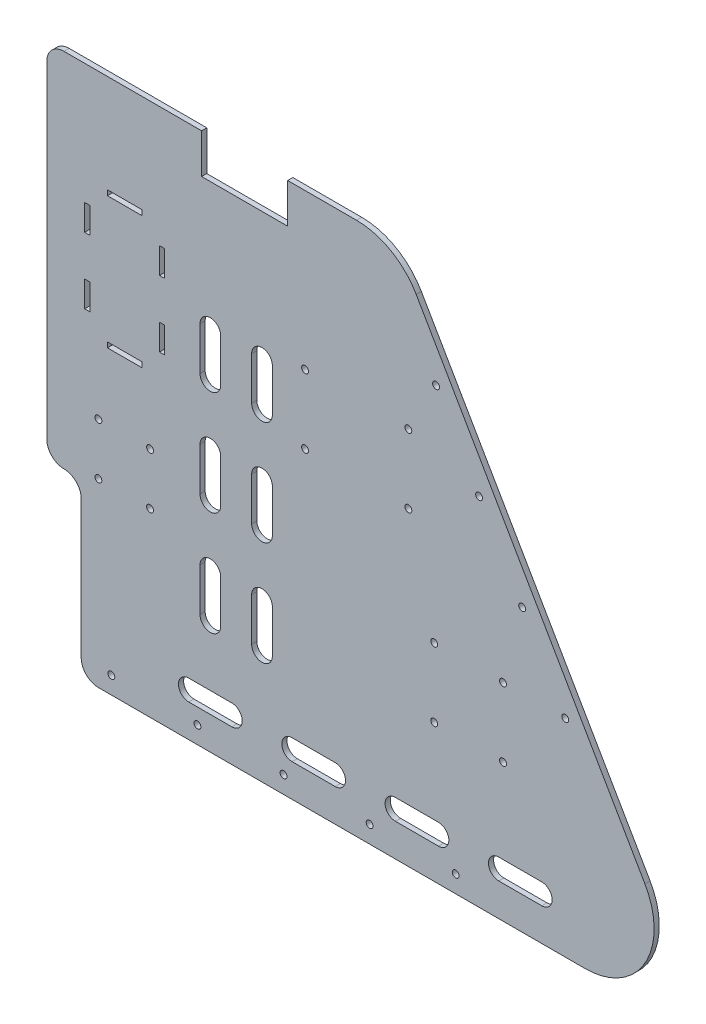
SolidWorks part; units mm, degrees
material "红木"
ref_plane "前视基准面" through (0, 0, 0) normal (0, 0, 1) x (1, 0, 0)
ref_plane "上视基准面" through (0, 0, 0) normal (0, 1, 0) x (1, 0, 0)
ref_plane "右视基准面" through (0, 0, 0) normal (1, 0, 0) x (0, 0, -1)
sketch "草图1" plane through (0, 0, 0) normal (0, 0, 1) x (1, 0, 0)
  line L0 (0, 0) -> (337.718, 0)
  line L1 (0, 0) -> (0, 310)
  line L2 (0, 310) -> (204.9274, 310)
  line L3 (239.5684, 290) -> (372.359, 60)
  line L4 (0, 66) -> (25, 66)
  line L5 (25, 66) -> (25, 310)
  line L7 (164.9274, 310) -> (114.9274, 310)
  line L8 (164.9274, 310) -> (164.9274, 287)
  line L9 (164.9274, 287) -> (114.9274, 287)
  line L10 (114.9274, 310) -> (114.9274, 287)
  arc A0 (337.718, 0) -> (372.359, 60) centre (337.718, 40) ccw
  arc A1 (239.5684, 290) -> (204.9274, 310) centre (204.9274, 270) ccw
  point P7 (407, 0)
  dimension "D4" = 40
  dimension "D1" = 407
  dimension "D2" = 310
  dimension "D3" = 60
  dimension "D5" = 25
  dimension "D6" = 66
  dimension "D7" = 23
  dimension "D8" = 50
  dimension "D9" = 40
extrude "凸台-拉伸1" add sketch "草图1" along normal blind 3 contours L3 A1 L2 L5 L4 L1 L0 A0 region at (170.7305, 136.5672, 0)
sketch "草图2" plane through (0, 0, 3) normal (0, 0, 1) x (1, 0, 0)
  line L0 (-53.0397, 10) -> (306.7383, 10) construction
  line L2 (0, 0) -> (337.718, 0) construction
  line L3 (0, 0) -> (0, 66) construction
  line L4 (337.718, 40) -> (19.1375, 223.9325) construction
  line L6 (262.5, 10) -> (212.5, 10) construction
  circle A0 centre (262.5, 10) radius 2
  circle A2 centre (212.5, 10) radius 2
  circle A3 centre (162.5, 10) radius 2
  circle A4 centre (112.5, 10) radius 2
  circle A5 centre (62.5, 10) radius 2
  circle A7 centre (251.0897, 250.0445) radius 2
  circle A8 centre (276.0897, 206.7432) radius 2
  circle A9 centre (301.0897, 163.4419) radius 2
  circle A10 centre (326.0897, 120.1407) radius 2
  dimension "D2" = 4
  dimension "D3" = 262.5
  dimension "D5" = 5
  dimension "D1" = 10
  dimension "D4" = 30
  dimension "D6" = 50
extrude "切除-拉伸1" cut sketch "草图2" against normal blind 10
sketch "草图3" plane through (0, 0, 3) normal (0, 0, 1) x (1, 0, 0)
  line L6 (0, 0) -> (45, 0)
  line L7 (0, 0) -> (0, 100)
  line L8 (0, 100) -> (45, 100)
  line L9 (45, 0) -> (45, 100)
  dimension "D1" = 100
  dimension "D2" = 45
extrude "切除-拉伸2" cut sketch "草图3" against normal through all
fillet "圆角1" radius 10 4 edges at (25, 310, 1.5) (25, 100, 1.5) (45, 100, 1.5) (45, 0, 1.5)
sketch "草图5" plane through (0, 0, 0) normal (0, 0, -1) x (-1, 0, 0)
  line L0 (-25, 110) -> (-25, 300) construction
  line L1 (-90.5, 250) -> (-50, 250) construction
  line L2 (-90.5, 250) -> (-90.5, 176.5) construction
  line L3 (-90.5, 176.5) -> (-50, 176.5) construction
  line L4 (-50, 250) -> (-50, 176.5) construction
  line L5 (-35, 310) -> (-114.9274, 310) construction
  line L6 (-70.25, 266.1718) -> (-70.25, 143.6965) construction
  line L7 (-90.5, 240) -> (-93.5, 240)
  line L8 (-90.5, 240) -> (-90.5, 225)
  line L9 (-90.5, 225) -> (-93.5, 225)
  line L10 (-93.5, 240) -> (-93.5, 225)
  line L11 (-90.5, 186.5) -> (-93.5, 186.5)
  line L12 (-90.5, 186.5) -> (-90.5, 201.5)
  line L13 (-90.5, 201.5) -> (-93.5, 201.5)
  line L14 (-93.5, 186.5) -> (-93.5, 201.5)
  line L15 (-50, 201.5) -> (-47, 201.5)
  line L16 (-47, 186.5) -> (-47, 201.5)
  line L17 (-50, 186.5) -> (-47, 186.5)
  line L18 (-50, 186.5) -> (-50, 201.5)
  line L19 (-50, 225) -> (-47, 225)
  line L20 (-47, 240) -> (-47, 225)
  line L21 (-50, 240) -> (-47, 240)
  line L22 (-50, 240) -> (-50, 225)
  line L24 (-60.25, 253) -> (-80.25, 253)
  line L25 (-60.25, 253) -> (-60.25, 250)
  line L26 (-60.25, 250) -> (-80.25, 250)
  line L27 (-80.25, 253) -> (-80.25, 250)
  line L28 (-60.25, 253) -> (-80.25, 250) construction
  line L29 (-60.25, 250) -> (-80.25, 253) construction
  line L30 (-80.25, 173.5) -> (-60.25, 173.5)
  line L31 (-80.25, 173.5) -> (-80.25, 176.5)
  line L32 (-80.25, 176.5) -> (-60.25, 176.5)
  line L33 (-60.25, 173.5) -> (-60.25, 176.5)
  line L34 (-80.25, 173.5) -> (-60.25, 176.5) construction
  line L35 (-80.25, 176.5) -> (-60.25, 173.5) construction
  point P14 (-92, 240)
  point P27 (-70.25, 251.5)
  point P32 (-70.25, 175)
  dimension "D1" = 73.5
  dimension "D2" = 40.5
  dimension "D3" = 25
  dimension "D4" = 60
  dimension "D5" = 15
  dimension "D6" = 3
  dimension "D7" = 10
  dimension "D8" = 15
  dimension "D9" = 3
  dimension "D10" = 10
  dimension "D11" = 20.25
  dimension "D12" = 3
  dimension "D13" = 20
  dimension "D14" = 3
  dimension "D15" = 20
extrude "大疆的电池" cut sketch "草图5" against normal blind 10
sketch "草图6" plane through (0, 0, 0) normal (0, 0, -1) x (-1, 0, 0)
  line L0 (-312.5, 25) -> (-287.5, 25) construction
  line L1 (-312.5, 31) -> (-287.5, 31)
  line L2 (-312.5, 19) -> (-287.5, 19)
  line L3 (-55, 0) -> (-337.718, 0) construction
  line L4 (-252.5, 19) -> (-227.5, 19)
  line L5 (-252.5, 31) -> (-227.5, 31)
  line L6 (-252.5, 25) -> (-227.5, 25) construction
  line L7 (-192.5, 19) -> (-167.5, 19)
  line L8 (-192.5, 31) -> (-167.5, 31)
  line L9 (-192.5, 25) -> (-167.5, 25) construction
  line L10 (-132.5, 19) -> (-107.5, 19)
  line L11 (-132.5, 31) -> (-107.5, 31)
  line L12 (-132.5, 25) -> (-107.5, 25) construction
  line L13 (-312.5, 19) -> (-252.5, 19) construction
  line L14 (-120, 212.5) -> (-120, 187.5) construction
  line L15 (-114, 212.5) -> (-114, 187.5)
  line L16 (-126, 212.5) -> (-126, 187.5)
  line L17 (-150, 212.5) -> (-150, 187.5) construction
  line L18 (-144, 212.5) -> (-144, 187.5)
  line L19 (-156, 212.5) -> (-156, 187.5)
  line L20 (-150, 151.8617) -> (-150, 126.8617) construction
  line L21 (-144, 151.8617) -> (-144, 126.8617)
  line L22 (-156, 151.8617) -> (-156, 126.8617)
  line L23 (-150, 91.2234) -> (-150, 66.2234) construction
  line L24 (-144, 91.2234) -> (-144, 66.2234)
  line L25 (-156, 91.2234) -> (-156, 66.2234)
  line L26 (-120, 151.8617) -> (-120, 126.8617) construction
  line L27 (-114, 151.8617) -> (-114, 126.8617)
  line L28 (-126, 151.8617) -> (-126, 126.8617)
  line L29 (-120, 91.2234) -> (-120, 66.2234) construction
  line L30 (-114, 91.2234) -> (-114, 66.2234)
  line L31 (-126, 91.2234) -> (-126, 66.2234)
  line L32 (-120, 212.5) -> (-150, 212.5) construction
  line L33 (-25, 110) -> (-25, 300) construction
  arc A0 (-312.5, 31) -> (-312.5, 19) centre (-312.5, 25) ccw
  arc A1 (-287.5, 19) -> (-287.5, 31) centre (-287.5, 25) ccw
  arc A2 (-252.5, 31) -> (-252.5, 19) centre (-252.5, 25) ccw
  arc A3 (-227.5, 19) -> (-227.5, 31) centre (-227.5, 25) ccw
  arc A4 (-192.5, 31) -> (-192.5, 19) centre (-192.5, 25) ccw
  arc A5 (-167.5, 19) -> (-167.5, 31) centre (-167.5, 25) ccw
  arc A6 (-132.5, 31) -> (-132.5, 19) centre (-132.5, 25) ccw
  arc A7 (-107.5, 19) -> (-107.5, 31) centre (-107.5, 25) ccw
  arc A8 (-114, 212.5) -> (-126, 212.5) centre (-120, 212.5) ccw
  arc A9 (-126, 187.5) -> (-114, 187.5) centre (-120, 187.5) ccw
  arc A10 (-144, 212.5) -> (-156, 212.5) centre (-150, 212.5) ccw
  arc A11 (-156, 187.5) -> (-144, 187.5) centre (-150, 187.5) ccw
  arc A12 (-144, 151.8617) -> (-156, 151.8617) centre (-150, 151.8617) ccw
  arc A13 (-156, 126.8617) -> (-144, 126.8617) centre (-150, 126.8617) ccw
  arc A14 (-144, 91.2234) -> (-156, 91.2234) centre (-150, 91.2234) ccw
  arc A15 (-156, 66.2234) -> (-144, 66.2234) centre (-150, 66.2234) ccw
  arc A16 (-114, 151.8617) -> (-126, 151.8617) centre (-120, 151.8617) ccw
  arc A17 (-126, 126.8617) -> (-114, 126.8617) centre (-120, 126.8617) ccw
  arc A18 (-114, 91.2234) -> (-126, 91.2234) centre (-120, 91.2234) ccw
  arc A19 (-126, 66.2234) -> (-114, 66.2234) centre (-120, 66.2234) ccw
  point P2 (-300, 25)
  point P13 (-240, 25)
  point P20 (-180, 25)
  point P27 (-120, 25)
  point P35 (-120, 200)
  point P44 (-150, 200)
  point P51 (-150, 139.3617)
  point P58 (-150, 78.7234)
  point P65 (-120, 139.3617)
  point P72 (-120, 78.7234)
  dimension "D1" = 6
  dimension "D7" = 6
  dimension "D14" = 60.6383
  dimension "D2" = 25
  dimension "D3" = 25
  dimension "D4" = 300
  dimension "D6" = 60
  dimension "D8" = 25
  dimension "D9" = 200
  dimension "D12" = 30
  dimension "D13" = 95
  dimension "D5" = 4
  dimension "D10" = 2
  dimension "D11" = 3
extrude "走线" cut sketch "草图6" against normal blind 10
sketch "草图7" plane through (0, 0, 0) normal (0, 0, -1) x (-1, 0, 0)
  line L0 (-417.3819, 120) -> (49.8568, 120) construction
  line L1 (-55, 0) -> (-337.718, 0) construction
  line L2 (-25, 110) -> (-25, 300) construction
  line L3 (-205, 374.7913) -> (-205, -82.4016) construction
  line L4 (-164.9274, 310) -> (-204.9274, 310) construction
  line L5 (-235, 220) -> (-235, 180) construction
  circle A0 centre (-290, 120) radius 2
  circle A1 centre (-250, 120) radius 2
  circle A2 centre (-290, 80) radius 2
  circle A3 centre (-250, 80) radius 2
  circle A4 centre (-85, 135) radius 2
  circle A5 centre (-55, 135) radius 2
  circle A6 centre (-55, 105) radius 2
  circle A7 centre (-85, 105) radius 2
  circle A8 centre (-235, 220) radius 2
  circle A9 centre (-235, 180) radius 2
  circle A10 centre (-175, 180) radius 2
  circle A11 centre (-175, 220) radius 2
  dimension "D2" = 4
  dimension "D3" = 4
  dimension "D4" = 40
  dimension "D5" = 225
  dimension "D7" = 40
  dimension "D8" = 4
  dimension "D9" = 15
  dimension "D10" = 60
  dimension "D12" = 30
  dimension "D14" = 4
  dimension "D15" = 30
  dimension "D16" = 90
  dimension "D1" = 120
  dimension "D13" = 180
  dimension "D18" = 40
  dimension "D6" = 2
  dimension "D11" = 2
  dimension "D17" = 2
extrude "切除-拉伸5" cut sketch "草图7" against normal blind 10
